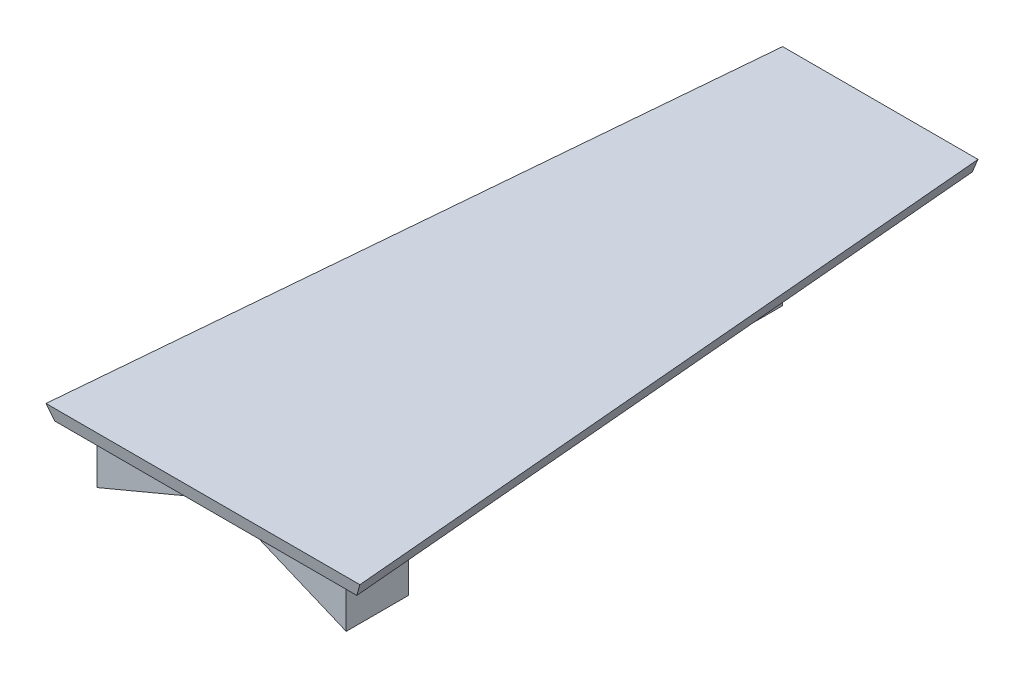
SolidWorks part; units mm, degrees
ref_plane "Ebene vorne" through (0, 0, 0) normal (0, 0, 1) x (1, 0, 0)
ref_plane "Ebene oben" through (0, 0, 0) normal (0, 1, 0) x (1, 0, 0)
ref_plane "Ebene rechts" through (0, 0, 0) normal (1, 0, 0) x (0, 0, -1)
sketch "Skizze1" plane through (0, 0, 0) normal (0, 1, 0) x (1, 0, 0)
  line L1 (-28.5, -61.5) -> (28.5, -61.5)
  line L2 (-28.5, -61.5) -> (-28.5, 61.5)
  line L3 (-28.5, 61.5) -> (28.5, 61.5)
  line L4 (28.5, -61.5) -> (28.5, 61.5)
  line L5 (-28.5, -61.5) -> (28.5, 61.5) construction
  line L6 (-28.5, 61.5) -> (28.5, -61.5) construction
  point P0 (0, 0)
  dimension "D1" = 57
  dimension "D2" = 123
extrude "Aufsatz-Linear austragen1" add sketch "Skizze1" along normal blind 2.5
sketch "Skizze2" plane through (28.5, 0, 0) normal (1, 0, 0) x (0, 0, -1)
  line L0 (-61.5, 2.5) -> (-61.5, 0)
  line L1 (55, 0) -> (-55, 0) construction
  line L2 (-61.5, 2.5) -> (-61.5, 0) construction
  line L3 (-61.5, 0) -> (-60.9686, 0)
  line L4 (-60.9686, 0) -> (-61.5, 2.5)
  dimension "D1" = 102
extrude "Schnitt-Linear austragen1" cut sketch "Skizze2" against normal through all
sketch "Skizze3" plane through (0, 2.5, 0) normal (0, 1, 0) x (1, 0, 0)
  line L0 (-28.5, -61.5) -> (-17.7389, 61.5)
  line L1 (28.5, 61.5) -> (-28.5, 61.5) construction
  line L2 (-17.7389, 61.5) -> (-28.5, 61.5)
  line L3 (-28.5, 61.5) -> (-28.5, -61.5)
  line L4 (28.5, -61.5) -> (17.7389, 61.5)
  line L5 (17.7389, 61.5) -> (28.5, 61.5)
  line L6 (28.5, 61.5) -> (28.5, -61.5)
  dimension "D1" = 95
  dimension "D2" = 95
extrude "Schnitt-Linear austragen2" cut sketch "Skizze3" against normal through all
ref_axis "Achse1" through (23.1194, 2.5, 0) along (0, -1, 0)
ref_plane "Ebene1" through (0.1756, 0, 2.0073) normal (0.0872, 0, 0.9962) x (0, -1, 0)
sketch "Skizze5" plane through (0.1756, 0, 2.0073) normal (0.0872, 0, 0.9962) x (0, -1, 0)
  line L0 (0.0086, 23.0315) -> (-2.5, 23.0315)
  line L1 (-2.5, 23.0315) -> (0, 23.0315) construction
  line L5 (0.0086, 23.0315) -> (0, 21.9959)
  line L6 (0, -33.659) -> (0, 23.0315) construction
  line L7 (0, 21.9959) -> (-2.5, 23.0315)
  line L8 (-2.5, -33.7516) -> (-2.5, 23.0315) construction
  dimension "D1" = 67.5
extrude "Schnitt-Linear austragen3" cut sketch "Skizze5" against normal through all and the other way through all
ref_axis "Achse2" through (-23.0962, -8.4274, -0.2657) along (0, 1, 0)
ref_plane "Ebene2" through (-0.1524, 0, 1.7416) normal (-0.0872, 0, 0.9962) x (0, 1, 0)
sketch "Skizze6" plane through (-0.1524, 0, 1.7416) normal (-0.0872, 0, 0.9962) x (0, 1, 0)
  line L1 (2.5, 23.0315) -> (0, 21.9959)
  line L2 (0, -55) -> (0, 55) construction
  line L3 (0, 21.9959) -> (0, 23.0315)
  line L4 (0, 23.0315) -> (2.5, 23.0315)
  line L5 (2.5, 23.0315) -> (2.5, -33.7516) construction
  dimension "D1" = 67.5
extrude "Schnitt-Linear austragen4" cut sketch "Skizze6" against normal through all and the other way through all
sketch "Skizze9" plane through (0, 0, 0) normal (0, -1, 0) x (1, 0, 0)
  line L6 (0, -61.5) -> (0, 60.9686) construction
  line L11 (16.6994, -61.5) -> (-16.6994, -61.5) construction
  line L12 (-27.414, 60.9686) -> (27.414, 60.9686) construction
  line L13 (0, 52.4686) -> (-26.6704, 52.4686) construction
  line L14 (-16.6994, -61.5) -> (-27.414, 60.9686) construction
  line L15 (-26.6704, 52.4686) -> (26.6704, 52.4686) construction
  line L16 (16.6994, -61.5) -> (27.414, 60.9686) construction
  line L17 (0, -19.5) -> (-20.3739, -19.5) construction
  line L18 (-20.3739, -19.5) -> (20.3739, -19.5) construction
  line L20 (22.6207, 58.1089) -> (-22.6207, 58.1089)
  line L21 (22.6207, 58.1089) -> (22.6207, 46.8283)
  line L22 (22.6207, 46.8283) -> (-22.6207, 46.8283)
  line L23 (-22.6207, 58.1089) -> (-22.6207, 46.8283)
  line L24 (22.6207, 58.1089) -> (-22.6207, 46.8283) construction
  line L25 (22.6207, 46.8283) -> (-22.6207, 58.1089) construction
  dimension "D1" = 42
  dimension "D2" = 8.5
extrude "Aufsatz-Linear austragen2" add sketch "Skizze9" along normal blind 13 contours L21 L20 L23 L22
sketch "Skizze11" plane through (0, 0, 46.8283) normal (0, 0, -1) x (-1, 0, 0)
  line L0 (-22.6207, -9.484) -> (0, 0)
  line L1 (-22.6207, -13) -> (-22.6207, 0) construction
  line L2 (-22.6207, 0) -> (22.6207, 0) construction
  line L3 (0, 0) -> (22.6207, -9.484)
  line L4 (22.6207, -13) -> (22.6207, 0) construction
  line L5 (22.6207, -9.484) -> (22.6207, -13)
  line L6 (22.6207, -13) -> (-22.6207, -13)
  line L7 (-22.6207, -13) -> (-22.6207, -9.484)
extrude "Schnitt-Linear austragen5" cut sketch "Skizze11" against normal blind 20
sketch "Skizze12" plane through (0, 0, 0) normal (0, -1, 0) x (1, 0, 0)
  line L0 (0, -61.5) -> (0, -2.1503) construction
  line L5 (16.6994, -61.5) -> (-16.6994, -61.5) construction
  line L6 (-20.3739, -19.5) -> (20.3739, -19.5) construction
  line L12 (-16.6994, -61.5) -> (-27.414, 60.9686) construction
  line L13 (16.6994, -61.5) -> (27.414, 60.9686) construction
  line L15 (18.0118, -15.2638) -> (-18.0118, -15.2638)
  line L16 (18.0118, -15.2638) -> (18.0118, -25.7362)
  line L17 (18.0118, -25.7362) -> (-18.0118, -25.7362)
  line L18 (-18.0118, -15.2638) -> (-18.0118, -25.7362)
  line L19 (18.0118, -15.2638) -> (-18.0118, -25.7362) construction
  line L24 (18.0118, -25.7362) -> (-18.0118, -15.2638) construction
  point P10 (0, -20.5)
  dimension "D2" = 41
extrude "Aufsatz-Linear austragen3" add sketch "Skizze12" along normal blind 5
sketch "Skizze13" plane through (0, 0, -25.7362) normal (0, 0, -1) x (-1, 0, 0)
  line L0 (-18.0118, -2.5) -> (-7.1831, 0)
  line L3 (-18.0118, -5) -> (-18.0118, 0) construction
  line L4 (18.0118, 0) -> (-18.0118, 0) construction
  line L5 (-7.1831, 0) -> (7.1831, 0)
  line L6 (7.1831, 0) -> (18.0118, -2.5)
  line L7 (18.0118, -5) -> (18.0118, 0) construction
  line L8 (18.0118, -2.5) -> (18.0118, -5)
  line L9 (18.0118, -5) -> (-18.0118, -5)
  line L10 (-18.0118, -5) -> (-18.0118, -2.5)
  dimension "D1" = 103
  dimension "D2" = 103
extrude "Schnitt-Linear austragen6" cut sketch "Skizze13" against normal blind 12
sketch "Skizze16" plane through (0, 0, 0) normal (0, -1, 0) x (1, 0, 0)
  line L0 (7.1831, -25.7362) -> (18.0118, -15.2638) construction
  line L1 (18.0118, -15.2638) -> (-18.0118, -15.2638) construction
  line L2 (-18.0118, -15.2638) -> (-7.1831, -25.7362) construction
  circle A0 centre (12.5975, -20.5) radius 3.1
  circle A1 centre (-12.5975, -20.5) radius 3.1
  dimension "D1" = 6.2
  dimension "D2" = 6.2
extrude "Schnitt-Linear austragen8" cut sketch "Skizze16" against normal blind 1.6 and the other way blind 0.5
ref_plane "Ebene7" through (0, -4.742, 0) normal (0, 1, 0) x (1, 0, 0)
sketch "Skizze17" plane through (0, -4.742, 0) normal (0, 1, 0) x (1, 0, 0)
  line L0 (22.6207, -58.1089) -> (11.3104, -46.8283) construction
  line L1 (0, -46.8283) -> (22.6207, -46.8283) construction
  line L2 (11.3104, -46.8283) -> (-11.3104, -58.1089) construction
  line L3 (-22.6207, -58.1089) -> (0, -58.1089) construction
  line L4 (-11.3104, -58.1089) -> (-22.6207, -46.8283) construction
  circle A0 centre (-16.9656, -52.4686) radius 3.1
  circle A1 centre (16.9656, -52.4686) radius 3.1
  dimension "D1" = 6.2
  dimension "D2" = 6.2
extrude "Schnitt-Linear austragen9" cut sketch "Skizze17" against normal blind 1 and the other way blind 1.1
